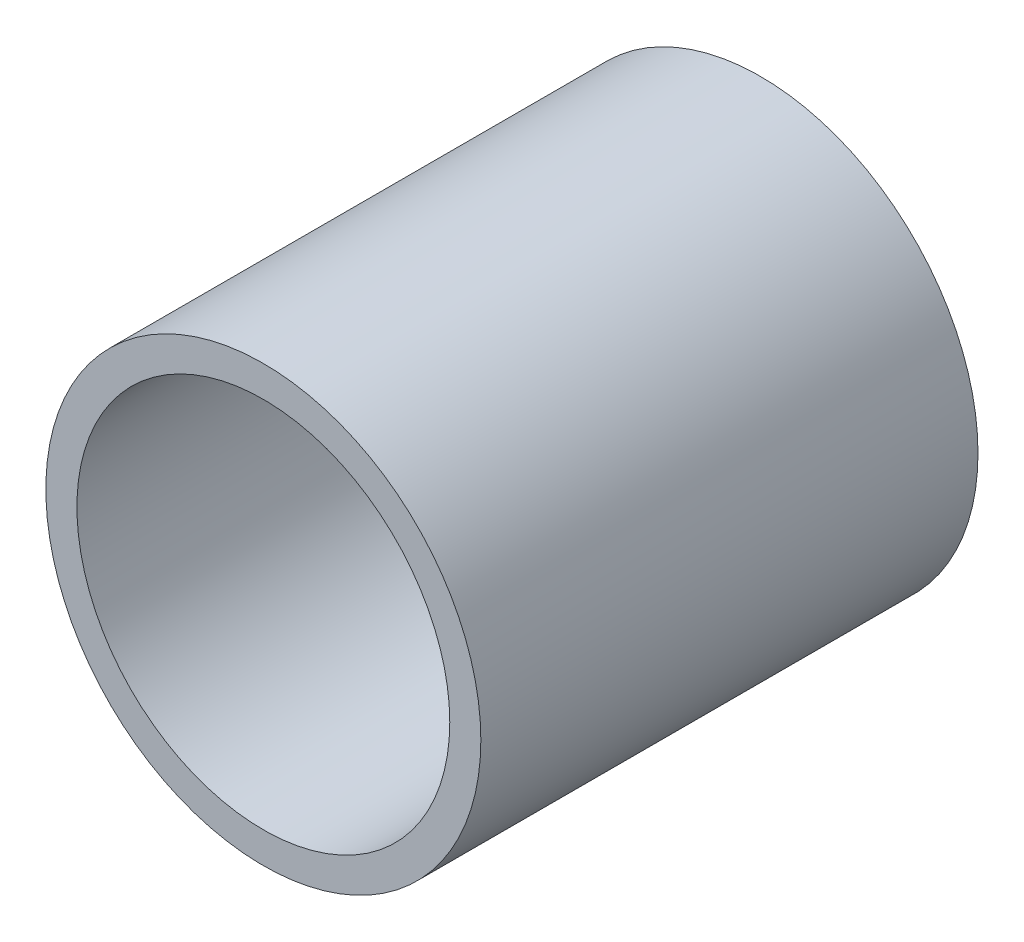
SolidWorks part; units mm, degrees
ref_plane "Front Plane" through (0, 0, 0) normal (0, 0, 1) x (1, 0, 0)
ref_plane "Top Plane" through (0, 0, 0) normal (0, 1, 0) x (1, 0, 0)
ref_plane "Right Plane" through (0, 0, 0) normal (1, 0, 0) x (0, 0, -1)
sketch "Sketch1" plane through (0, 0, 0) normal (0, 0, 1) x (1, 0, 0)
  circle A0 centre (0, 0) radius 19.05
  circle A1 centre (0, 0) radius 22.225
  dimension "D1" = 38.1
  dimension "D2" = 44.45
extrude "Boss-Extrude1" add sketch "Sketch1" against normal blind 50.8 contours A1 | A0
